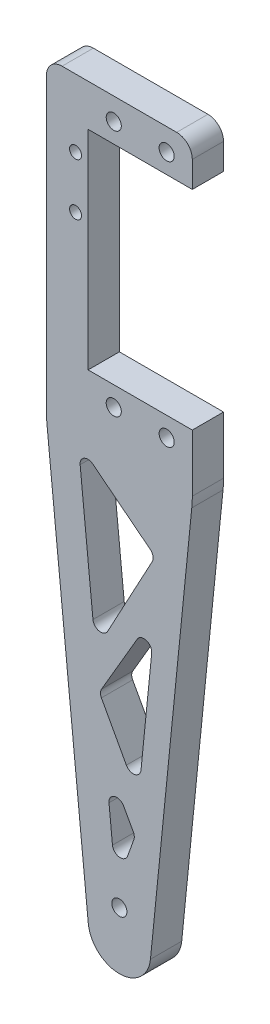
SolidWorks part; units mm, degrees
material "ABS"
ref_plane "Front" through (0, 0, 0) normal (0, 0, 1) x (1, 0, 0)
ref_plane "Top" through (0, 0, 0) normal (0, 1, 0) x (1, 0, 0)
ref_plane "Right" through (0, 0, 0) normal (1, 0, 0) x (0, 0, -1)
sketch "Esquisse1" plane through (0, 0, 0) normal (0, 0, 1) x (1, 0, 0)
  line L0 (-14, -30) -> (-5.97, -110)
  line L1 (-14, 30) -> (14, 30)
  line L2 (-14, 30) -> (-14, -30)
  line L4 (14, 30) -> (14, 22)
  line L5 (14, -18) -> (14, -30)
  line L6 (14, 22) -> (-6, 22)
  line L8 (5.97, -110) -> (14, -30)
  line L10 (14, -18) -> (-6, -18)
  line L11 (-6, 22) -> (-6, -18)
  arc A0 (-5.97, -110) -> (5.97, -110) centre (0, -109.4008) ccw
  point P0 (0, 0)
  point P1 (0, 0)
  point P3 (0, 0)
  point P14 (-14, 0)
  point P16 (-14, -30)
  point P17 (14, -30)
  point P18 (0, -90)
  point P19 (0, -90)
  point P20 (0, -90)
  point P21 (0, 30)
  point P22 (-2.1818, -90)
  point P23 (0, 0)
  point P24 (0, -90)
  point P25 (0, 0)
  dimension "D2" = 6
  dimension "D1" = 60
  dimension "D3" = 28
  dimension "D5" = 20
  dimension "D6" = 40
  dimension "D7" = 8
  dimension "D8" = 80
extrude "Boss.-Extru.1" add sketch "Esquisse1" along normal blind 6
fillet "Congé1" radius 3 2 edges at (-14, 30, 3) (14, 30, 3)
fillet "Congé2" radius 20 2 edges at (14, -30, 3) (-14, -30, 3)
sketch "Esquisse2" plane through (0, 0, 6) normal (0, 0, 1) x (1, 0, 0)
  line L0 (14, -18) -> (-6, -18) construction
  circle A1 centre (9.08, -21.75) radius 1.45
  circle A2 centre (-1.08, -21.75) radius 1.45
  circle A3 centre (-1.08, 25.75) radius 1.45
  circle A4 centre (9.08, 25.75) radius 1.45
  point P4 (4, -18)
  dimension "D1" = 5.08
  dimension "D2" = 3.75
  dimension "D3" = 2.9
  dimension "D5" = 2
  dimension "D4" = 2
extrude "Enlèv. mat.-Extru.1" cut sketch "Esquisse2" against normal up to next
sketch "Esquisse3" plane through (0, 0, 6) normal (0, 0, 1) x (1, 0, 0)
  line L6 (-7.8866, -31.0175) -> (-4.5844, -63.9162)
  line L7 (-4.5844, -63.9162) -> (6.8947, -42.6374)
  line L8 (6.8947, -42.6374) -> (-7.8866, -31.0175)
  line L15 (6.8947, -52.1218) -> (-3.8542, -70.5115)
  line L16 (-4.5844, -63.9162) -> (-2.7281, -80.6823) construction
  line L17 (-3.8542, -70.5115) -> (3.6639, -84.3099)
  line L18 (3.6639, -84.3099) -> (6.8947, -52.1218)
  line L19 (-2.7281, -80.6823) -> (-0.6632, -101.2543)
  line L20 (-0.6632, -101.2543) -> (3.0064, -91.0782)
  line L21 (3.0064, -91.0782) -> (-2.7281, -80.6823)
  line L23 (5.97, -110) -> (13.9, -30.9962) construction
  line L24 (-13.9, -30.9962) -> (-5.97, -110) construction
  point P13 (0, 0)
  point P14 (6.8947, -52.1218)
  point P15 (-2.7281, -80.6823)
extrude "Enlèv. mat.-Extru.2" cut sketch "Esquisse3" against normal up to next
fillet "Congé3" radius 1.5 9 edges at (6.8947, -42.6374, 3) (-4.5844, -63.9162, 3) (-7.8866, -31.0175, 3) (3.0064, -91.0782, 3) (-2.7281, -80.6823, 3) (-0.6632, -101.2543, 3) (3.6639, -84.3099, 3) (-3.8542, -70.5115, 3) (6.8947, -52.1218, 3)
sketch "Esquisse4" plane through (0, 0, 6) normal (0, 0, 1) x (1, 0, 0)
  circle A0 centre (0, -104.4008) radius 1.45
  arc A1 (-5.97, -110) -> (5.97, -110) centre (0, -109.4008) ccw construction
  point P2 (0, -108.7779)
  point P6 (0, -115.4008)
  dimension "D1" = 2.9
  dimension "D2" = 11
extrude "Enlèv. mat.-Extru.3" cut sketch "Esquisse4" against normal blind 6
sketch "Esquisse5" plane through (0, 0, 6) normal (0, 0, 1) x (1, 0, 0)
  line L0 (-6, 22) -> (14, 22) construction
  line L1 (-6, -18) -> (-6, 22) construction
  circle A0 centre (-8.41, 17) radius 1.15
  circle A1 centre (-8.41, 7) radius 1.15
  dimension "D1" = 2.3
  dimension "D2" = 5
  dimension "D3" = 2.41
  dimension "D4" = 2
extrude "Enlèv. mat.-Extru.4" cut sketch "Esquisse5" against normal blind 6
